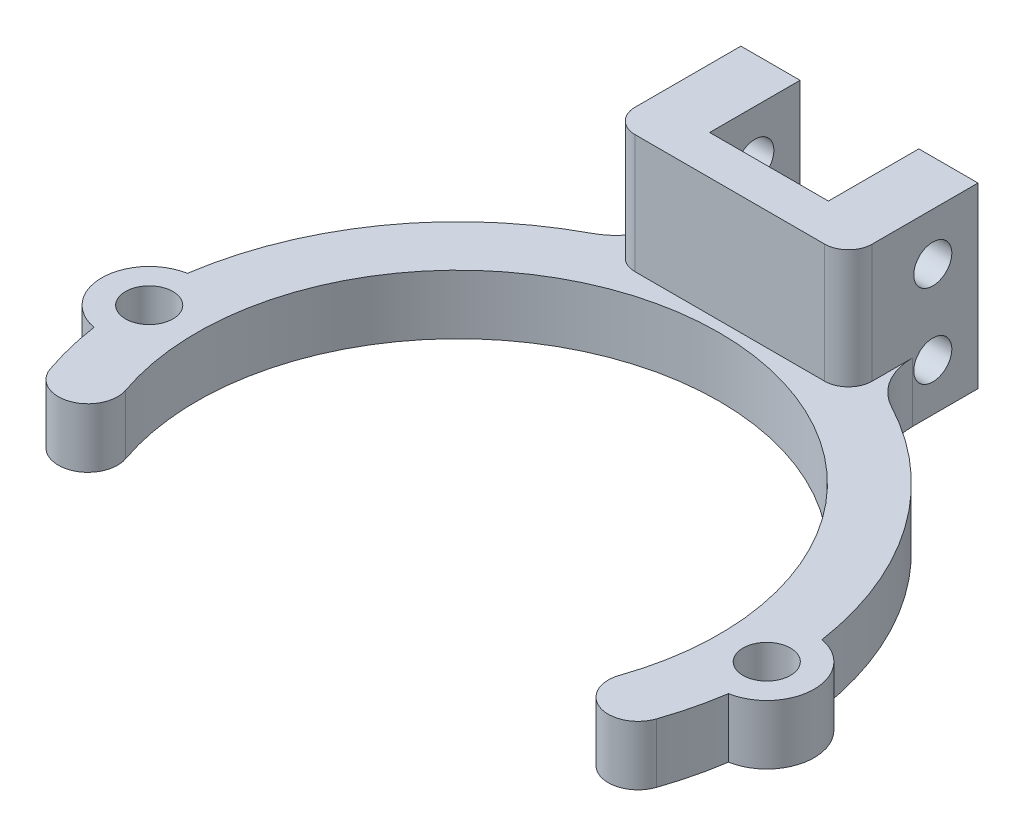
SolidWorks part; units mm, degrees
ref_plane "前视基准面" through (0, 0, 0) normal (0, 0, 1) x (1, 0, 0)
ref_plane "上视基准面" through (0, 0, 0) normal (0, 1, 0) x (1, 0, 0)
ref_plane "右视基准面" through (0, 0, 0) normal (1, 0, 0) x (0, 0, -1)
sketch "草图1" plane through (0, 0, 0) normal (0, 1, 0) x (1, 0, 0)
  line L0 (-28.9941, -8) -> (32.5349, -8) construction
  line L1 (0, 0) -> (0, -8) construction
  line L2 (0, 22) -> (0, 27) construction
  line L3 (0, 0) -> (0, 22) construction
  arc A0 (20.7941, -7.1837) -> (-20.7941, -7.1837) centre (0, 0) ccw
  circle A4 centre (-26, 0) radius 2
  arc A5 (-26.7115, 3.9362) -> (-26.7115, -3.9362) centre (-26, 0) ccw
  circle A7 centre (0, 0) radius 24.5 construction
  arc A8 (26.7115, 3.9362) -> (-26.7115, 3.9362) centre (0, 0) ccw
  arc A9 (-26.7115, -3.9362) -> (-25.52, -8.8163) centre (0, 0) ccw
  arc A10 (20.7941, -7.1837) -> (25.52, -8.8163) centre (23.1571, -8) ccw
  arc A11 (-25.52, -8.8163) -> (-20.7941, -7.1837) centre (-23.1571, -8) ccw
  arc A12 (25.52, -8.8163) -> (26.7115, -3.9362) centre (0, 0) ccw
  arc A13 (26.7115, 3.9362) -> (26.7115, -3.9362) centre (26, 0) cw
  circle A14 centre (26, 0) radius 2
  point P16 (0, 24.5)
  point P18 (-23.1571, -8)
  point P19 (23.1571, -8)
extrude "凸台-拉伸1" add sketch "草图1" along normal blind 5
sketch "草图3" plane through (0, 0, 0) normal (0, 1, 0) x (1, 0, 0)
  line L0 (0, 0) -> (0, 30) construction
  line L1 (-5, 33.807) -> (-9.9829, 33.807)
  line L2 (9.9829, 22.8964) -> (-9.9829, 22.8964)
  line L3 (9.9829, 22.8964) -> (9.9829, 33.807)
  line L4 (9.9829, 33.807) -> (5, 33.807)
  line L5 (-9.9829, 22.8964) -> (-9.9829, 33.807)
  line L6 (9.9829, 22.8964) -> (-9.9829, 33.807) construction
  line L7 (9.9829, 33.807) -> (-9.9829, 22.8964) construction
  line L8 (5, 26.193) -> (-5, 26.193)
  line L9 (5, 26.193) -> (5, 33.807)
  line L10 (-5, 26.193) -> (-5, 33.807)
  line L11 (5, 26.193) -> (-5, 33.807) construction
  line L12 (5, 33.807) -> (-5, 26.193) construction
  point P6 (0, 30)
  point P7 (0, 30)
extrude "凸台-拉伸2" add sketch "草图3" along normal blind 15
sketch "草图5" plane through (0, 5, 0) normal (0, 1, 0) x (1, 0, 0)
  line L0 (9.9829, 33.807) -> (5, 33.807) construction
  line L1 (-5, 26.193) -> (5, 26.193)
  line L2 (-5, 26.193) -> (-5, 33.807)
  line L3 (-5, 33.807) -> (5, 33.807)
  line L4 (5, 26.193) -> (5, 33.807)
  line L5 (5, 33.807) -> (5, 26.193) construction
extrude "切除-拉伸2" cut sketch "草图5" against normal through all
sketch "草图4" plane through (-9.9829, 0, 0) normal (-1, 0, 0) x (0, 0, 1)
  circle A0 centre (-30, 4) radius 1.6
  circle A1 centre (-30, 11) radius 1.6
  point P4 (0, 0)
  point P5 (-29.4468, 3.2384)
  point P6 (-29.042, 11.8093)
extrude "切除-拉伸1" cut sketch "草图4" against normal through all
fillet "圆角2" radius 5 2 edges at (9.9829, 2.5, -25.0867) (-9.9829, 2.5, -25.0867)
fillet "圆角3" radius 2 2 edges at (9.9829, 10, -22.8964) (-9.9829, 10, -22.8964)
